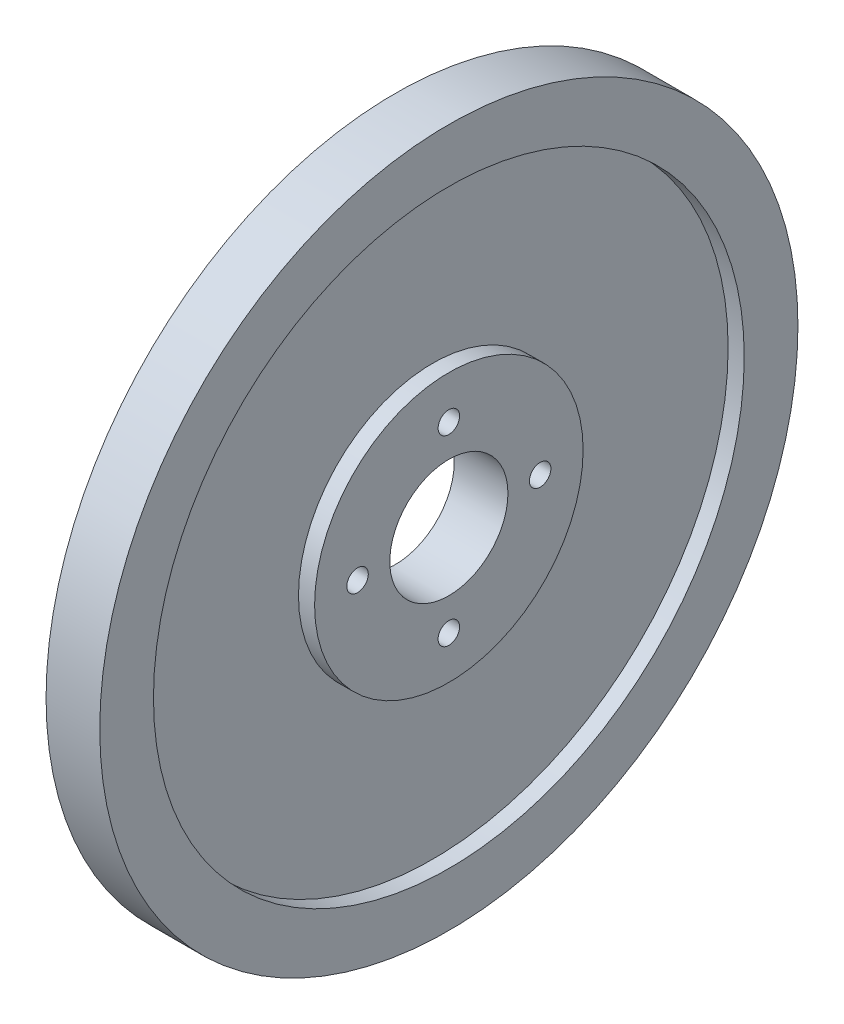
SolidWorks part; units mm, degrees
material "2024-T4"
ref_plane "Front Plane" through (0, 0, 0) normal (0, 0, 1) x (1, 0, 0)
ref_plane "Top Plane" through (0, 0, 0) normal (0, 1, 0) x (1, 0, 0)
ref_plane "Right Plane" through (0, 0, 0) normal (1, 0, 0) x (0, 0, -1)
sketch "Sketch1" plane through (0, 0, 0) normal (1, 0, 0) x (0, 0, -1)
  circle A1 centre (0, 0) radius 65
  dimension "D1" = 130
extrude "Boss-Extrude1" add sketch "Sketch1" along normal mid plane 10
sketch "Sketch3" plane through (5, 0, 0) normal (1, 0, 0) x (0, 0, -1)
  circle A0 centre (0, 0) radius 11
  dimension "D1" = 22
extrude "Cut-Extrude2" cut sketch "Sketch3" against normal through all
sketch "Sketch4" [suppressed] plane through (5, 0, 0) normal (1, 0, 0) x (0, 0, -1)
  line L0 (0, 0) -> (0, 5) construction
  circle A1 centre (0, 5) radius 1.5
  circle A2 centre (5, 0) radius 1.5
  circle A3 centre (0, -5) radius 1.5
  circle A4 centre (-5, 0) radius 1.5
  point P13 (0, 0)
  dimension "D1" = 5
  dimension "D2" = 3
  dimension "D3" = 4
extrude "Cut-Extrude3" [suppressed] cut sketch "Sketch4" against normal through all
sketch "Sketch5" plane through (5, 0, 0) normal (1, 0, 0) x (0, 0, -1)
  line L0 (0, 0) -> (0, 17) construction
  circle A2 centre (0, 17) radius 2
  circle A3 centre (17, 0) radius 2
  circle A4 centre (0, -17) radius 2
  circle A5 centre (-17, 0) radius 2
  point P12 (0, 0)
  dimension "D2" = 4
  dimension "D1" = 17
  dimension "D4" = 17
  dimension "D5" = 17
  dimension "D3" = 4
sketch "Sketch6" [suppressed] plane through (5, 0, 0) normal (1, 0, 0) x (0, 0, -1)
  circle A12 centre (0, 0) radius 16
  circle A13 centre (0, 0) radius 55
  dimension "D1" = 110
  dimension "D2" = 32
extrude "Cut-Extrude4" [suppressed] cut sketch "Sketch6" against normal blind 3 contours A13 A12
extrude "Cut-Extrude5" cut sketch "Sketch5" against normal through all contours A2 | A5 | A4 | A3
sketch "Sketch7" [suppressed] plane through (5, 0, 0) normal (1, 0, 0) x (0, 0, -1)
  circle A0 centre (0, 0) radius 8
  dimension "D1" = 16
extrude "Cut-Extrude6" [suppressed] cut sketch "Sketch7" against normal through all
ref_plane "Plane1" [suppressed] through (0, 0, 0) normal (1, 0, 0) x (0, 0, -1)
sketch "Sketch8" [suppressed] plane through (0, 0, 0) normal (1, 0, 0) x (0, 0, -1)
  circle A0 centre (0, 0) radius 6.5
  circle A1 centre (0, 0) radius 8 construction
  circle A2 centre (0, 0) radius 8
  dimension "D1" = 13
extrude "Boss-Extrude2" [suppressed] add sketch "Sketch8" along normal mid plane 1.5
mirror "Mirror1" [suppressed] about plane through (0, 0, 0) normal (1, 0, 0)
sketch "Sketch9" plane through (5, 0, 0) normal (1, 0, 0) x (0, 0, -1)
  circle A0 centre (0, 0) radius 25
  circle A1 centre (0, 0) radius 55
  dimension "D1" = 110
  dimension "D2" = 50
extrude "Cut-Extrude7" cut sketch "Sketch9" against normal blind 3
mirror "Mirror2" about plane through (0, 0, 0) normal (1, 0, 0) of "Cut-Extrude7"
